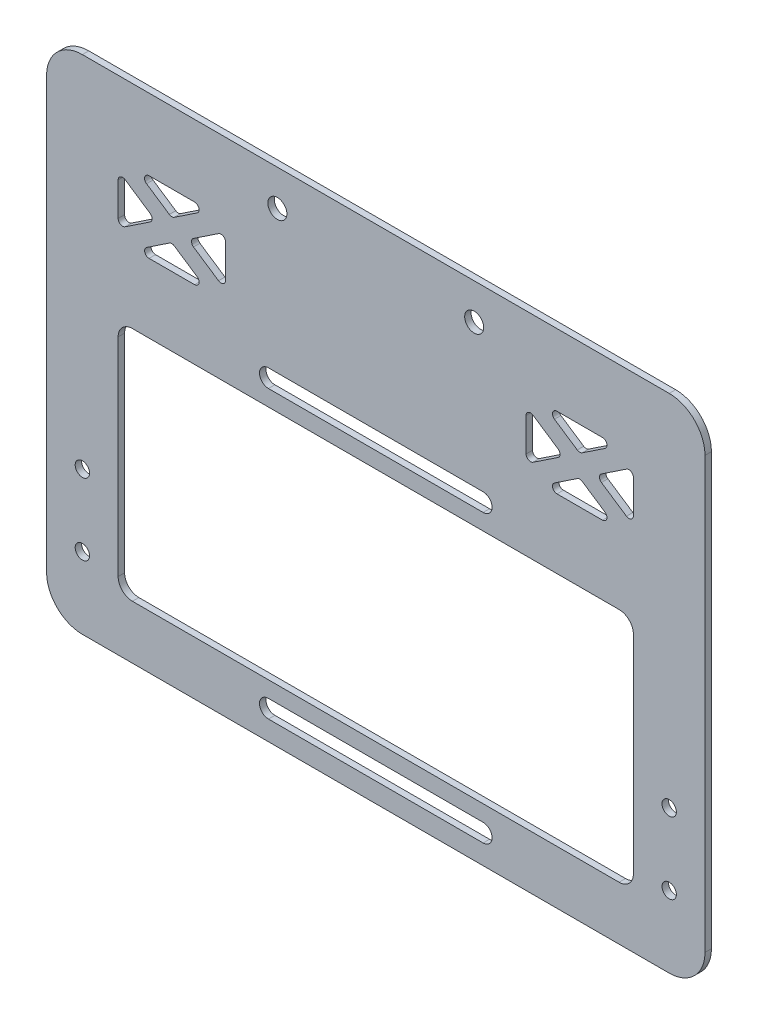
SolidWorks part; units mm, degrees
ref_plane "Front Plane" through (0, 0, 0) normal (0, 0, 1) x (1, 0, 0)
ref_plane "Top Plane" through (0, 0, 0) normal (0, 1, 0) x (1, 0, 0)
ref_plane "Right Plane" through (0, 0, 0) normal (1, 0, 0) x (0, 0, -1)
sketch "Sketch1" plane through (0, 0, 0) normal (0, 0, 1) x (1, 0, 0)
  line L1 (-116.84, 89.1002) -> (116.84, 89.1002)
  line L2 (-116.84, 89.1002) -> (-116.84, -89.1002)
  line L3 (-116.84, -89.1002) -> (116.84, -89.1002)
  line L4 (116.84, 89.1002) -> (116.84, -89.1002)
  line L5 (-116.84, 89.1002) -> (116.84, -89.1002) construction
  line L6 (-116.84, -89.1002) -> (116.84, 89.1002) construction
  line L7 (-86.36, 13.7698) -> (86.36, 13.7698)
  line L8 (-91.44, 8.6898) -> (-91.44, -64.9702)
  line L9 (-86.36, -70.0502) -> (86.36, -70.0502)
  line L10 (91.44, 8.6898) -> (91.44, -64.9702)
  line L11 (-91.44, 13.7698) -> (91.44, -70.0502) construction
  line L12 (-91.44, -70.0502) -> (91.44, 13.7698) construction
  arc A0 (86.36, -70.0502) -> (91.44, -64.9702) centre (86.36, -64.9702) ccw
  arc A1 (86.36, 13.7698) -> (91.44, 8.6898) centre (86.36, 8.6898) cw
  arc A2 (-91.44, 8.6898) -> (-86.36, 13.7698) centre (-86.36, 8.6898) cw
  arc A3 (-86.36, -70.0502) -> (-91.44, -64.9702) centre (-86.36, -64.9702) cw
  point P0 (0, 0)
  point P5 (0, -28.1402)
  dimension "D7" = 5.08
  dimension "D1" = 25.4
  dimension "D3" = 182.88
  dimension "D4" = 83.82
  dimension "D5" = 19.05
  dimension "D6" = 233.68
extrude "Boss-Extrude1" add sketch "Sketch1" along normal blind 2.286
sketch "Sketch2" plane through (0, 0, 2.286) normal (0, 0, 1) x (1, 0, 0)
  line L0 (38.1, 22.6598) -> (-38.1, 22.6598) construction
  line L1 (38.1, 19.4848) -> (-38.1, 19.4848)
  line L2 (38.1, 25.8348) -> (-38.1, 25.8348)
  line L3 (-91.44, 8.6898) -> (-91.44, -64.9702) construction
  line L4 (-91.44, -28.1402) -> (91.44, -28.1402) construction
  line L5 (-91.44, 8.6898) -> (-91.44, -64.9702) construction
  line L6 (91.44, -64.9702) -> (91.44, 8.6898) construction
  line L7 (38.1, -78.9402) -> (-38.1, -78.9402) construction
  line L8 (38.1, -75.7652) -> (-38.1, -75.7652)
  line L9 (38.1, -82.1152) -> (-38.1, -82.1152)
  arc A0 (38.1, 19.4848) -> (38.1, 25.8348) centre (38.1, 22.6598) ccw
  arc A1 (-38.1, 25.8348) -> (-38.1, 19.4848) centre (-38.1, 22.6598) ccw
  arc A2 (38.1, -75.7652) -> (38.1, -82.1152) centre (38.1, -78.9402) cw
  arc A3 (-38.1, -82.1152) -> (-38.1, -75.7652) centre (-38.1, -78.9402) cw
  point P2 (0, 22.6598)
  point P7 (-91.44, -28.1402)
  point P19 (0, -78.9402)
  dimension "D1" = 76.2
  dimension "D2" = 50.8
  dimension "D3" = 6.35
extrude "Cut-Extrude1" cut sketch "Sketch2" against normal through all
hole_wizard "1/4 Clearance Hole2" positions "Sketch8" profile "Sketch7" hole size "1/4" standard "ANSI Inch" end condition through all
sketch "Sketch8" plane through (0, 0, 2.286) normal (0, 0, 1) x (1, 0, 0)
  line L3 (-34.925, 76.4002) -> (34.925, 76.4002) construction
  line L5 (116.84, 89.1002) -> (-116.84, 89.1002) construction
  line L6 (-31.75, 76.4002) -> (31.75, 76.4002) construction
  point P0 (-34.925, 76.4002)
  point P2 (34.925, 76.4002)
  point P17 (0, 76.4002)
  dimension "D1" = 69.85
  dimension "D2" = 12.7
sketch "Sketch7" plane through (-34.925, 76.4002, 2.286) normal (1, 0, 0) x (0, -1, 0)
  line L0 (0, 0) -> (0, 2.286)
  line L1 (0, 2.286) -> (3.3782, 2.286)
  line L2 (3.3782, 2.286) -> (3.3782, 0)
  line L5 (3.3782, 0) -> (0, 0)
  line L11 (0, -6.35) -> (0, 107.95) construction
  dimension "Thru Hole Dia." = 6.7564
  dimension "Thru Hole Depth" = 2.286
fillet "Fillet1" radius 12.7 4 edges at (-116.84, 89.1002, 1.143) (116.84, 89.1002, 1.143) (-116.84, -89.1002, 1.143) (116.84, -89.1002, 1.143)
sketch "Sketch9" plane through (0, 0, 2.286) normal (0, 0, 1) x (1, 0, 0)
  line L0 (-104.14, -89.1002) -> (104.14, -89.1002) construction
  line L3 (-91.44, 8.6898) -> (-91.44, -64.9702) construction
  line L4 (91.44, -64.9702) -> (91.44, 8.6898) construction
  circle A0 centre (-104.14, -63.7002) radius 2.5527
  circle A1 centre (104.14, -63.7002) radius 2.5527
  circle A2 centre (104.14, -38.3002) radius 2.5527
  circle A3 centre (-104.14, -38.3002) radius 2.5527
  dimension "D3" = 5.1054
  dimension "D1" = 25.4
  dimension "D2" = 25.4
  dimension "D4" = 25.4
  dimension "D5" = 12.7
  dimension "D6" = 12.7
  dimension "D7" = 25.4
extrude "Cut-Extrude2" cut sketch "Sketch9" against normal through all
sketch "Sketch10" plane through (0, 0, 2.286) normal (0, 0, 1) x (1, 0, 0)
  line L0 (104.14, 89.1002) -> (-104.14, 89.1002) construction
  line L1 (-91.44, 63.7002) -> (-53.34, 63.7002)
  line L2 (-91.44, 63.7002) -> (-91.44, 38.3002)
  line L3 (-91.44, 38.3002) -> (-53.34, 38.3002)
  line L4 (-53.34, 63.7002) -> (-53.34, 38.3002)
  line L5 (-91.44, 63.7002) -> (-53.34, 38.3002) construction
  line L6 (-91.44, 38.3002) -> (-53.34, 63.7002) construction
  line L7 (53.34, 63.7002) -> (91.44, 63.7002)
  line L8 (53.34, 63.7002) -> (53.34, 38.3002)
  line L9 (53.34, 38.3002) -> (91.44, 38.3002)
  line L10 (91.44, 63.7002) -> (91.44, 38.3002)
  line L11 (53.34, 63.7002) -> (91.44, 38.3002) construction
  line L12 (53.34, 38.3002) -> (91.44, 63.7002) construction
  line L13 (-116.84, 76.4002) -> (-116.84, -76.4002) construction
  line L14 (116.84, -76.4002) -> (116.84, 76.4002) construction
  line L15 (-93.2012, 61.0584) -> (-55.1012, 35.6584)
  line L16 (-89.6788, 35.6584) -> (-51.5788, 61.0584)
  line L17 (55.1012, 35.6584) -> (93.2012, 61.0584)
  line L18 (51.5788, 61.0584) -> (89.6788, 35.6584)
  line L19 (-89.6788, 66.342) -> (-51.5788, 40.942)
  line L20 (-93.2012, 40.942) -> (-55.1012, 66.342)
  line L21 (51.5788, 40.942) -> (89.6788, 66.342)
  line L22 (55.1012, 66.342) -> (93.2012, 40.942)
  point P0 (-72.39, 51.0002)
  point P5 (72.39, 51.0002)
  dimension "D1" = 38.1
  dimension "D2" = 25.4
  dimension "D3" = 25.4
  dimension "D4" = 25.4
  dimension "D5" = 25.4
  dimension "D6" = 3.175
  dimension "D7" = 3.175
extrude "Cut-Extrude3" cut sketch "Sketch10" against normal through all contours L19 L20 L1 | L2 L20 L15 | L16 L3 L15 | L16 L19 L4 | L18 L17 L9 | L8 L21 L18 | L7 L22 L21 | L17 L22 L10 region at (-72.39, 60.7388, 2.286) region at (-86.9979, 51.0002, 2.286) region at (-57.7821, 51.0002, 2.286) region at (-72.39, 41.2616, 2.286) region at (72.39, 60.7388, 2.286) region at (57.7821, 51.0002, 2.286) region at (86.9979, 51.0002, 2.286) region at (72.39, 41.2616, 2.286)
fillet "Fillet2" radius 1.5875 24 edges at (91.44, 59.8843, 1.143) (91.44, 42.1161, 1.143) (78.1138, 51.0002, 1.143) (85.7162, 63.7002, 1.143) (59.0638, 63.7002, 1.143) (72.39, 54.8161, 1.143) (66.6662, 51.0002, 1.143) (53.34, 59.8843, 1.143) (53.34, 42.1161, 1.143) (85.7162, 38.3002, 1.143) (72.39, 47.1843, 1.143) (59.0638, 38.3002, 1.143) (-78.1138, 51.0002, 1.143) (-91.44, 59.8843, 1.143) (-91.44, 42.1161, 1.143) (-59.0638, 63.7002, 1.143) (-85.7162, 63.7002, 1.143) (-72.39, 54.8161, 1.143) (-53.34, 59.8843, 1.143) (-53.34, 42.1161, 1.143) (-66.6662, 51.0002, 1.143) (-72.39, 47.1843, 1.143) (-59.0638, 38.3002, 1.143) (-85.7162, 38.3002, 1.143)
